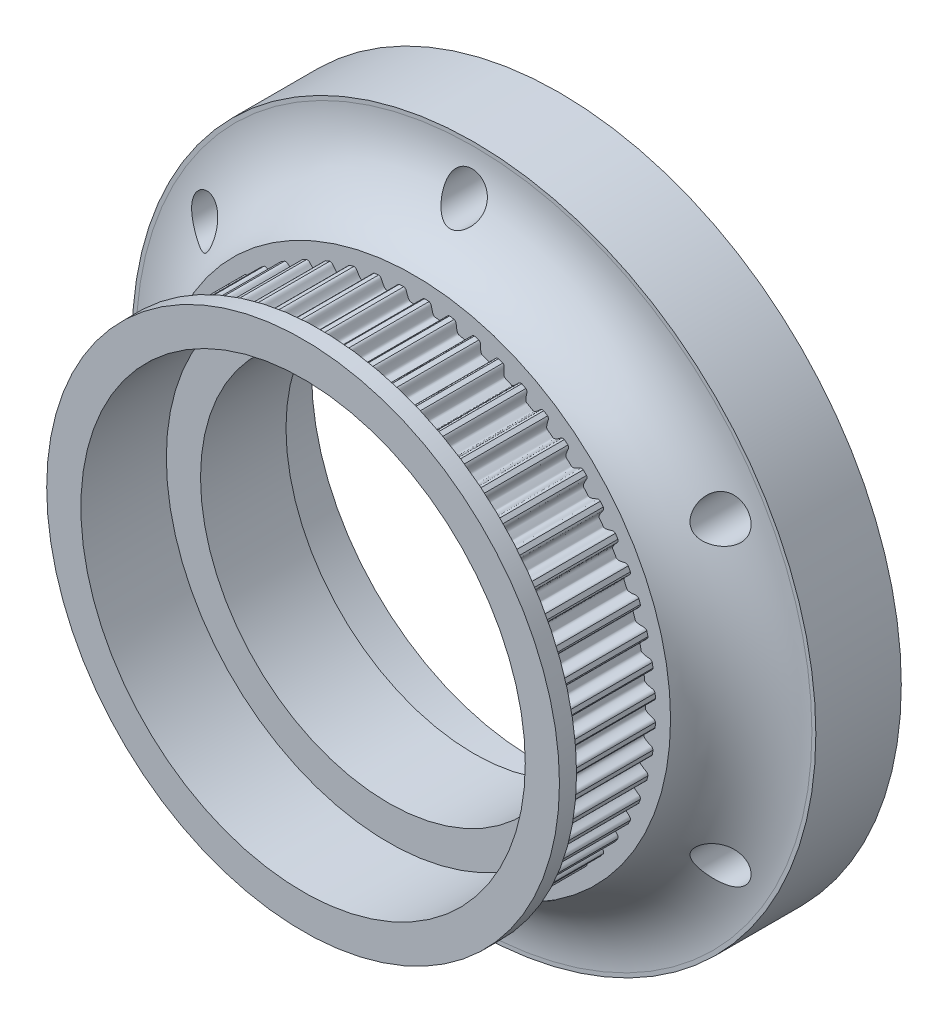
SolidWorks part; units mm, degrees
note: '?' marks a value the reader was unsure of.
ref_plane "前视基准面" through (0, 0, 0) normal (0, 0, 1) x (1, 0, 0)
ref_plane "上视基准面" through (0, 0, 0) normal (0, 1, 0) x (1, 0, 0)
ref_plane "右视基准面" through (0, 0, 0) normal (1, 0, 0) x (0, 0, -1)
other "Configuration Table"
ref_axis "基准轴1" through (0, 0, 55) along (0, 0, -1)?
sketch "SketchRevolveGearBelt01" plane through (0, 0, 0) normal (1, 0, 0) x (0, 0, -1)
  line L0 (0, 0) -> (1, 0) construction
  line L1 (9.774, 0) -> (9.774, 26.2479)
  line L2 (9.774, 26.2479) -> (9.012, 26.2479)
  line L3 (9.012, 26.2479) -> (9.012, 28.4963)
  line L4 (9.012, 28.4963) -> (9.48, 29.6263)
  line L5 (9.48, 29.6263) -> (8.7761, 29.9179)
  line L6 (8.7761, 29.9179) -> (8.25, 28.6479)
  line L7 (8.25, 28.6479) -> (8.25, 28.2529)
  line L8 (8.25, 28.2529) -> (-8.25, 28.2529)
  line L9 (-8.25, 28.2529) -> (-8.25, 28.6479)
  line L10 (-8.25, 28.6479) -> (-8.7761, 29.9179)
  line L11 (-8.7761, 29.9179) -> (-9.48, 29.6263)
  line L12 (-9.48, 29.6263) -> (-9.012, 28.4963)
  line L13 (-9.012, 28.4963) -> (-9.012, 26.2479)
  line L14 (-9.012, 26.2479) -> (-9.774, 26.2479)
  line L15 (-9.774, 26.2479) -> (-9.774, 0)
  line L16 (-9.774, 0) -> (9.774, 0)
  dimension "GearBeltFlange1OutsideLength" = 2.2484
  dimension "GearBeltFlange1X" = 0.468
  dimension "GearBeltFlange1Y" = 1.13
  dimension "GearBeltFlangeThickness" = 0.762
  dimension "GearBeltFlangeInside" = 0.395
  dimension "GearBeltOutsideDiameter" = 28.2529
  dimension "GearBeltFlange2X" = 0.468
revolve "Gates_PowerGrip_GT_3mm, 15mm Belt Width" add sketch "SketchRevolveGearBelt01" angle 360 about L0
sketch "SketchToothGearBelt01" plane through (0, 0, 0) normal (0, 0, 1) x (1, 0, 0)
  arc A0 (28.2367, 1.2911) -> (28.2367, -1.2911) centre (0, 0) cw
  spline S0 degree 3 poles (28.2367, -1.2911) (28.2364, -1.2655) (28.2322, -1.227) (28.2194, -1.1773) (28.2062, -1.141) (28.1896, -1.1062) (28.1697, -1.0732) (28.1468, -1.0422) (28.121, -1.0136) (28.0925, -0.9876) (28.0617, -0.9645) (28.0288, -0.9444) (27.9942, -0.9274) (27.9308, -0.905) (27.8508, -0.8809) (27.7571, -0.8512) (27.6784, -0.8247) (27.6045, -0.7983) (27.5353, -0.7718) (27.4709, -0.7454) (27.4113, -0.7189) (27.3564, -0.6925) (27.3063, -0.666) (27.2609, -0.6396) (27.2202, -0.6131) (27.1843, -0.5867) (27.1532, -0.5602) (27.1268, -0.5337) (27.1051, -0.5071) (27.0881, -0.4805) (27.0759, -0.4538) (27.0684, -0.4269) (27.0651, -0.3755) (27.0699, -0.3) (27.0701, -0.2) (27.0712, -0.1) (27.0714, 0) (27.0712, 0.1) (27.0701, 0.2) (27.0699, 0.3) (27.0651, 0.3755) (27.0684, 0.4269) (27.0759, 0.4538) (27.0881, 0.4805) (27.1051, 0.5071) (27.1268, 0.5337) (27.1532, 0.5602) (27.1843, 0.5867) (27.2202, 0.6131) (27.2609, 0.6396) (27.3063, 0.666) (27.3564, 0.6925) (27.4113, 0.7189) (27.4709, 0.7454) (27.5353, 0.7718) (27.6045, 0.7983) (27.6784, 0.8247) (27.7571, 0.8512) (27.8508, 0.8809) (27.9308, 0.905) (27.9942, 0.9274) (28.0288, 0.9444) (28.0617, 0.9645) (28.0925, 0.9876) (28.121, 1.0136) (28.1468, 1.0422) (28.1697, 1.0732) (28.1896, 1.1062) (28.2062, 1.141) (28.2194, 1.1773) (28.2322, 1.227) (28.2364, 1.2655) (28.2367, 1.2911) knots 0 0 0 0 0.019513 0.029269 0.039026 0.048782 0.058538 0.068295 0.078051 0.087808 0.097564 0.10732 0.117077 0.126833 0.158411 0.180602 0.201644 0.221544 0.240311 0.257955 0.274488 0.289925 0.304283 0.317585 0.32986 0.341142 0.351478 0.360929 0.369573 0.377512 0.384878 0.391837 0.398582 0.423956 0.449304 0.474652 0.5 0.525348 0.550696 0.576044 0.601418 0.608163 0.615122 0.622488 0.630427 0.639071 0.648522 0.658858 0.67014 0.682415 0.695717 0.710075 0.725512 0.742045 0.759689 0.778456 0.798356 0.819398 0.841589 0.873167 0.882923 0.89268 0.902436 0.912192 0.921949 0.931705 0.941462 0.951218 0.960974 0.970731 0.980487 1 1 1 1
extrude "ToothExtrudeCutGearBelt01" cut sketch "SketchToothGearBelt01" against normal blind 8.25 and the other way blind 8.25
pattern_circular "Tooth Pattern, 60" count 60 every 6 about axis through (0, 0, 55) along (0, 0, -1) of "ToothExtrudeCutGearBelt01"
sketch "BoreRevolveSketch" plane through (0, 0, 0) normal (1, 0, 0) x (0, 0, -1)
  line L0 (0, 0) -> (1, 0) construction
  line L1 (-9.774, 0) -> (9.774, 0)
  line L2 (9.774, 0) -> (9.774, 5)
  line L3 (9.774, 5) -> (-9.774, 5)
  line L4 (-9.774, 5) -> (-9.774, 0)
  dimension "TaperSide1" = 5
  dimension "TaperSide2" = 5
revolve "BoreRevolveCut" cut sketch "BoreRevolveSketch" angle 360 about L0
sketch "AuxiliarySketchGearBelt01" plane through (0, 0, 0) normal (0, 0, 1) x (1, 0, 0)
  circle A0 centre (0, 0) radius 28.6479 construction
  dimension "PitchDiameter" = 57.2958
sketch "草图5" plane through (0, 0, 9.774) normal (0, 0, 1) x (1, 0, 0)
  circle A0 centre (0, 0) radius 35.7331
extrude "切除-拉伸2" cut sketch "草图5" against normal blind 4.55
sketch "草图6" plane through (0, 0, -9.774) normal (0, 0, -1) x (-1, 0, 0)
  circle A0 centre (0, 0) radius 40.0055
extrude "切除-拉伸3" cut sketch "草图6" against normal blind 4
sketch "草图7" plane through (0, 0, -5.774) normal (0, 0, -1) x (-1, 0, 0)
  circle A0 centre (0, 0) radius 30
  dimension "D1" = 60
extrude "凸台-拉伸1" add sketch "草图7" along normal blind 2
sketch "草图8" plane through (0, 0, 5.224) normal (0, 0, 1) x (1, 0, 0)
  circle A0 centre (0, 0) radius 30
extrude "凸台-拉伸2" add sketch "草图8" along normal blind 2
sketch "草图9" plane through (0, 0, 7.224) normal (0, 0, 1) x (1, 0, 0)
  circle A0 centre (0, 0) radius 26
  dimension "D1" = 52
extrude "切除-拉伸4" cut sketch "草图9" against normal through all
sketch "草图10" plane through (0, 0, -7.774) normal (0, 0, -1) x (-1, 0, 0)
  circle A0 centre (0, 0) radius 30
  circle A1 centre (0, 0) radius 26
extrude "凸台-拉伸3" add sketch "草图10" along normal blind 5
sketch "草图11" plane through (0, 0, -12.774) normal (0, 0, -1) x (-1, 0, 0)
  circle A0 centre (0, 0) radius 40
  circle A1 centre (0, 0) radius 26
  dimension "D1" = 80
extrude "凸台-拉伸4" add sketch "草图11" along normal blind 10
sketch "草图12" plane through (0, 0, -22.774) normal (0, 0, -1) x (-1, 0, 0)
  circle A0 centre (0, 0) radius 35
  circle A1 centre (0, 35) radius 2.4
  circle A2 centre (30.3109, 17.5) radius 2.4
  circle A3 centre (30.3109, -17.5) radius 2.4
  circle A4 centre (0, -35) radius 2.4
  circle A5 centre (-30.3109, -17.5) radius 2.4
  circle A6 centre (-30.3109, 17.5) radius 2.4
  point P18 (0, 0)
  dimension "D1" = 70
  dimension "D2" = 4.8
  dimension "D3" = 6
extrude "切除-拉伸5" cut sketch "草图12" against normal through all contours A1 | A2 | A3 | A4 | A5 | A6
fillet "圆角1" radius 10 1 edges at (-30, 0, -12.774)
ref_plane "基准面1" through (0, 0, -12.774) normal (0, 0, -1) x (-1, 0, 0)
sketch "草图13" plane through (0, 0, -12.774) normal (0, 0, -1) x (-1, 0, 0)
  circle A0 centre (0, 0) radius 26
  circle A1 centre (0, 0) radius 20
  dimension "D1" = 40
extrude "凸台-拉伸5" add sketch "草图13" against normal blind 10
sketch "草图14" plane through (0, 0, -2.774) normal (0, 0, 1) x (1, 0, 0)
  circle A0 centre (0, 0) radius 22
  dimension "D1" = 44
extrude "切除-拉伸6" cut sketch "草图14" against normal through all
sketch "草图15" plane through (0, 0, -22.774) normal (0, 0, -1) x (-1, 0, 0)
  circle A0 centre (0, 0) radius 31
  dimension "D1" = 62
extrude "切除-拉伸7" cut sketch "草图15" against normal blind 3
